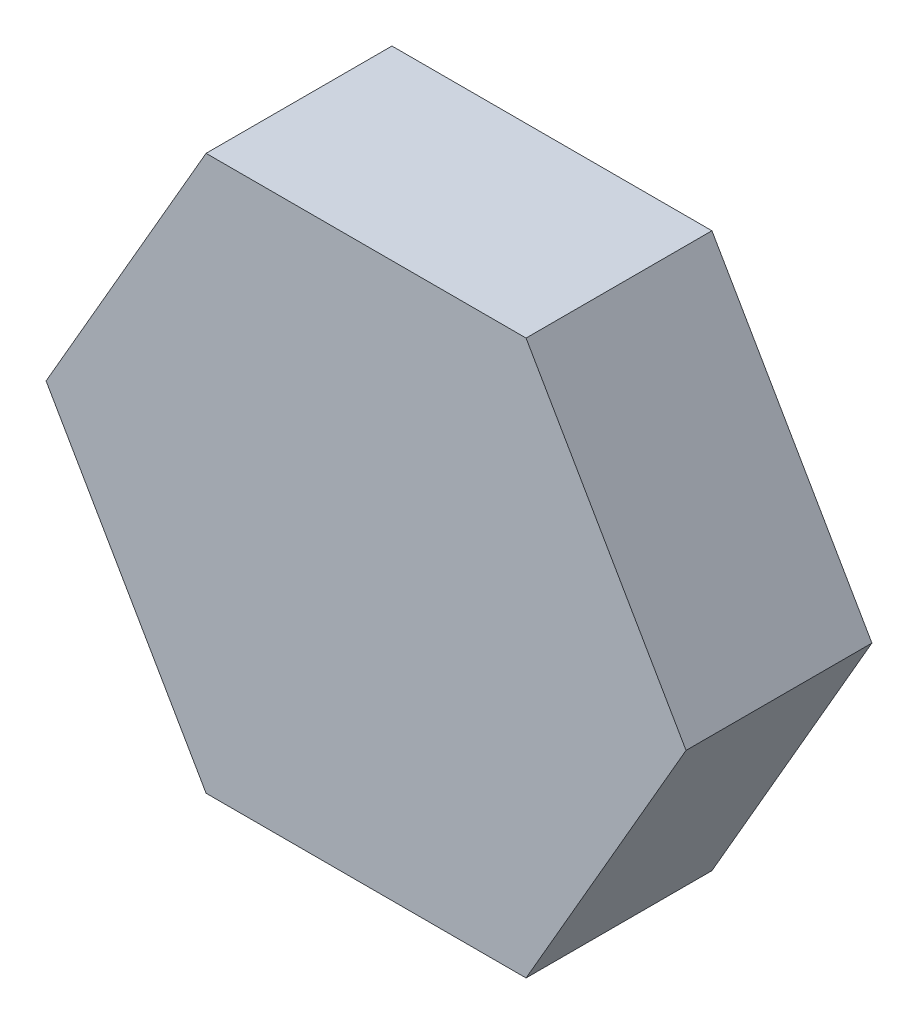
SolidWorks part; units mm, degrees
ref_plane "Front Plane" through (0, 0, 0) normal (0, 0, 1) x (1, 0, 0)
ref_plane "Top Plane" through (0, 0, 0) normal (0, 1, 0) x (1, 0, 0)
ref_plane "Right Plane" through (0, 0, 0) normal (1, 0, 0) x (0, 0, -1)
sketch "Sketch1" plane through (0, 0, 0) normal (0, 0, 1) x (1, 0, 0)
  line L1 (25.8227, 0) -> (12.9113, 22.3631)
  line L2 (12.9113, 22.3631) -> (-12.9113, 22.3631)
  line L3 (-12.9113, 22.3631) -> (-25.8227, 0)
  line L4 (-25.8227, 0) -> (-12.9113, -22.3631)
  line L5 (-12.9113, -22.3631) -> (12.9113, -22.3631)
  line L6 (12.9113, -22.3631) -> (25.8227, 0)
  circle A0 centre (0, 0) radius 22.3631 construction
extrude "Boss-Extrude1" add sketch "Sketch1" along normal blind 15
sketch "Sketch2" plane through (0, 0, 0) normal (0, 0, 1) x (1, 0, 0)
  circle A0 centre (0, 0) radius 9.017
extrude "Cut-Extrude1" cut sketch "Sketch2" along normal blind 12
thread "Thread1" pitch 1.5875 method extrude profile "Thread Profile2" start angle 0, offset 0, length 10, pitch 1.5875, diameter 18.034
ref_plane "Plane2" through (9.017, 0, 0) normal (0, -1, 0) x (1, 0, 0)
sketch "Thread Profile2" plane through (9.017, 0, 0) normal (0, -1, 0) x (1, 0, 0)
  line L0 (0, 0) -> (0, 1.5875) construction
  line L11 (0, 0) -> (0, 1.3891)
  line L12 (0, 1.3891) -> (-0.8593, 0.893)
  line L13 (-0.8593, 0.893) -> (-0.8593, 0.4961)
  line L15 (-0.8593, 0.4961) -> (0, 0)
  line L17 (-0.8593, 0.6945) -> (0, 0.6945) construction
  point P2 (0, 0)
  dimension "Pitch" = 1.5875
  dimension "Profile_Angle" = 60
  dimension "Profile_Land" = 0.3969
  dimension "Profile_Height" = 0.8593
